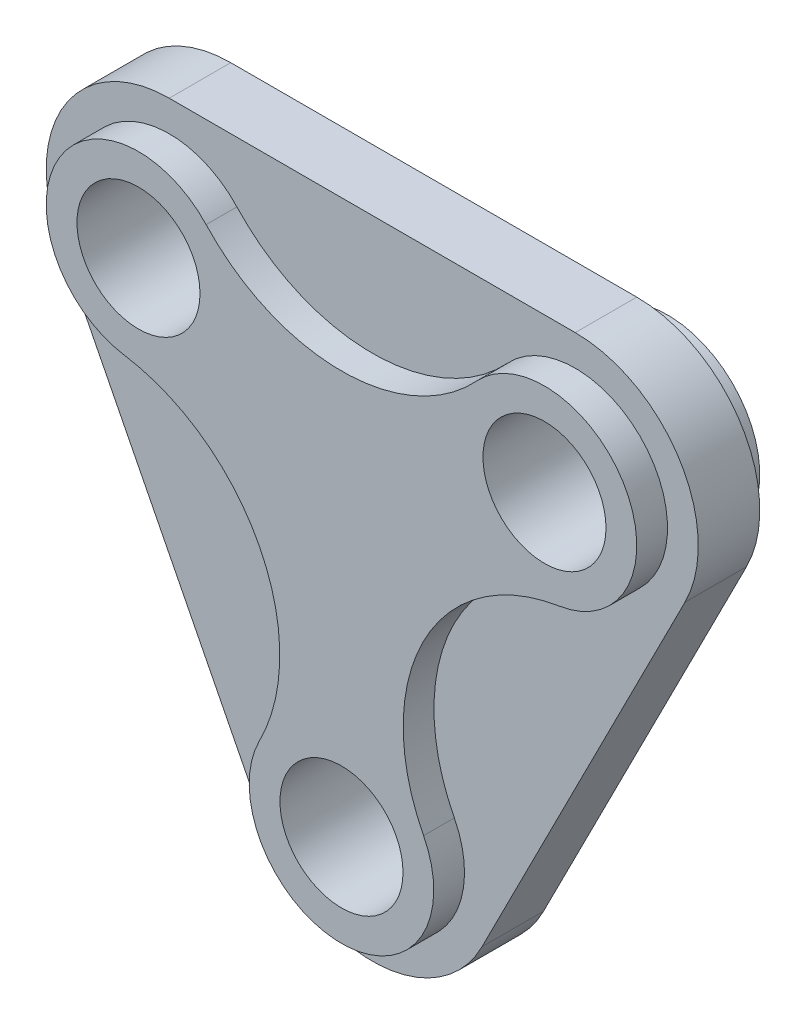
SolidWorks part; units mm, degrees
ref_plane "Front Plane" through (0, 0, 0) normal (0, 0, 1) x (1, 0, 0)
ref_plane "Top Plane" through (0, 0, 0) normal (0, 1, 0) x (1, 0, 0)
ref_plane "Right Plane" through (0, 0, 0) normal (1, 0, 0) x (0, 0, -1)
sketch "Sketch1" plane through (0, 0, 0) normal (0, 0, 1) x (1, 0, 0)
  line L0 (0, 0) -> (0, 49819.6344) construction
  line L1 (0, 0) -> (49819.6344, 0) construction
  line L2 (-50.8333, 55.9462) -> (-17.8333, -9.0538)
  line L3 (50.8333, 55.9462) -> (17.8333, -9.0538)
  line L4 (-33, 85) -> (33, 85)
  arc A0 (-13.3441, 6.851) -> (13.3441, 6.851) centre (0, 0) ccw
  circle A1 centre (0, 0) radius 10
  arc A2 (-17.8333, -9.0538) -> (17.8333, -9.0538) centre (0, 0) ccw
  circle A3 centre (-33, 65) radius 10
  arc A4 (-22, 75.198) -> (-35.3441, 50.1843) centre (-33, 65) ccw
  arc A5 (-33, 85) -> (-50.8333, 55.9462) centre (-33, 65) ccw
  circle A6 centre (33, 65) radius 10
  arc A7 (22, 75.198) -> (35.3441, 50.1843) centre (33, 65) cw
  arc A8 (33, 85) -> (50.8333, 55.9462) centre (33, 65) cw
  arc A9 (-35.3441, 50.1843) -> (-13.3441, 6.851) centre (-40.0322, 20.5529) cw
  arc A10 (35.3441, 50.1843) -> (13.3441, 6.851) centre (40.0322, 20.5529) ccw
  arc A11 (-22, 75.198) -> (22, 75.198) centre (0, 95.5941) ccw
  dimension "D1" = 20
  dimension "D2" = 30
  dimension "D3" = 40
  dimension "D4" = 33
  dimension "D6" = 30
  dimension "D7" = 30
  dimension "D5" = 65
extrude "Boss-Extrude1" add sketch "Sketch1" along normal mid plane 20 contours A11 A4 A9 A0 A10 A7 A1 A3 A6 region at (0, 44.0916, 0)
extrude "Boss-Extrude2" add sketch "Sketch1<3>" along normal mid plane 10 contours A8 L4 A5 L2 A2 L3 A4 A11 A7 A10 A0 A9 region at (-48.7736, 74.6819, 0)
sketch "Sketch1<3>" plane through (0, 0, 0) normal (0, 0, 1) x (1, 0, 0) same geometry as "Sketch1"
